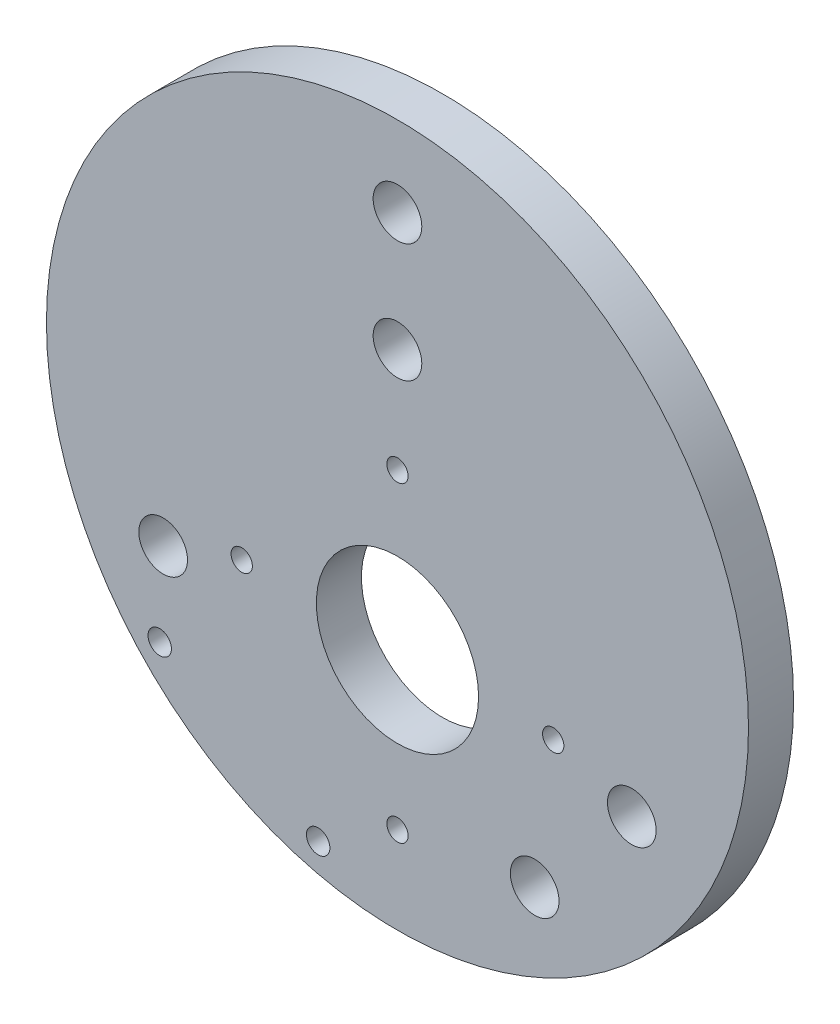
SolidWorks part; units mm, degrees
ref_plane "Front Plane" through (0, 0, 0) normal (0, 0, 1) x (1, 0, 0)
ref_plane "Top Plane" through (0, 0, 0) normal (0, 1, 0) x (1, 0, 0)
ref_plane "Right Plane" through (0, 0, 0) normal (1, 0, 0) x (0, 0, -1)
sketch "Sketch1" plane through (0, 0, 0) normal (0, 0, 1) x (1, 0, 0)
  circle A0 centre (0, 0) radius 49.4665
  dimension "D1" = 98.933
extrude "Boss-Extrude1" add sketch "Sketch1" along normal blind 6.35
sketch "Sketch2" plane through (0, 0, 6.35) normal (0, 0, 1) x (1, 0, 0)
  line L0 (0, -37.1877) -> (0, 6.7077) construction
  line L1 (-21.9477, -15.24) -> (0, 6.7077)
  line L2 (-21.9477, -15.24) -> (0, -37.1877)
  line L3 (0, -37.1877) -> (21.9477, -15.24)
  line L4 (0, 6.7077) -> (21.9477, -15.24)
  line L5 (0, -15.24) -> (12.0918, -15.24) construction
  point P4 (0, -15.24)
  dimension "D1" = 31.0388
  dimension "D2" = 31.0388
  dimension "D3" = 15.24
  dimension "D4" = 90
hole_wizard "M3 Screw Hole - Ø3.0mm Dowel Hole" positions "Sketch3" profile "Sketch4" hole size "Ø3.0" standard "ANSI Metric" end condition through all
sketch "Sketch3" plane through (0, 0, 6.35) normal (0, 0, 1) x (1, 0, 0)
  point P0 (0, 6.7077)
  point P3 (-21.9477, -15.24)
  point P6 (0, -37.1877)
  point P9 (21.9477, -15.24)
sketch "Sketch4" plane through (0, 6.7077, 6.35) normal (1, 0, 0) x (0, -1, 0)
  line L0 (0, 0) -> (0, 6.35)
  line L1 (0, 6.35) -> (1.5, 6.35)
  line L2 (1.5, 6.35) -> (1.5, 0)
  line L5 (1.5, 0) -> (0, 0)
  line L11 (0, -6.35) -> (0, 107.95) construction
  dimension "Thru Hole Dia." = 3
  dimension "Thru Hole Depth" = 6.35
sketch "Sketch5" plane through (0, 0, 6.35) normal (0, 0, 1) x (1, 0, 0)
  line L0 (0, -37.1877) -> (0, 6.7077) construction
  line L1 (-29.9941, -15.24) -> (0, 14.7541)
  line L2 (-29.9941, -15.24) -> (0, -45.2341)
  line L3 (0, -45.2341) -> (29.9941, -15.24)
  line L4 (0, 14.7541) -> (29.9941, -15.24)
  line L5 (-29.9941, -15.24) -> (29.9941, -15.24) construction
  line L6 (0, -45.2341) -> (0, 14.7541) construction
  line L7 (-19.3974, 4.1574) -> (0, -15.24) construction
  line L8 (0, -15.24) -> (19.3974, -15.24) construction
  line L9 (0, -15.24) -> (19.3974, -34.6374) construction
  line L10 (0, -15.24) -> (-3.0533, -18.2933) construction
  line L11 (-3.0533, -18.2933) -> (16.3441, -37.6906) construction
  line L12 (0, -15.24) -> (-19.3974, -34.6374) construction
  line L13 (0, -15.24) -> (-18.3197, 3.0797) construction
  line L14 (-18.3197, 3.0797) -> (0, 21.3994) construction
  circle A0 centre (0, 21.3994) radius 3.429
  circle A1 centre (16.3441, -37.6906) radius 3.429
  circle A2 centre (-19.3974, -34.6374) radius 3.429
  point P0 (0, -15.24)
  point P7 (0, -15.24)
  dimension "D3" = 27.432
  dimension "D5" = 27.432
  dimension "D9" = 6.858
  dimension "D1" = 42.418
  dimension "D2" = 4.318
  dimension "D4" = 42.418
  dimension "D6" = 27.432
  dimension "D7" = 135
  dimension "D8" = 25.908
sketch "Sketch6" plane through (0, 0, 6.35) normal (0, 0, 1) x (1, 0, 0)
  line L0 (0, 38.1282) -> (-33.02, -19.0641) construction
  line L1 (-33.02, -19.0641) -> (33.02, -19.0641) construction
  line L2 (33.02, -19.0641) -> (0, 38.1282) construction
  line L3 (-33.02, -19.0641) -> (0, 0) construction
  line L4 (0, 0) -> (33.02, -19.0641) construction
  line L5 (0, 0) -> (0, 38.1282) construction
  circle A0 centre (0, 38.1282) radius 3.429
  circle A1 centre (-33.02, -19.0641) radius 3.429
  circle A2 centre (33.02, -19.0641) radius 3.429
  dimension "D1" = 6.858
  dimension "D2" = 66.04
  dimension "D3" = 60
  dimension "D4" = 60
extrude "Cut-Extrude2" cut sketch "Sketch6" against normal through all
sketch "Sketch7" plane through (0, 0, 6.35) normal (0, 0, 1) x (1, 0, 0)
  line L0 (0, -37.1877) -> (0, 6.7077) construction
  circle A0 centre (0, -15.24) radius 11.43
  point P4 (0, -15.24)
  dimension "D1" = 22.86
extrude "Cut-Extrude3" cut sketch "Sketch7" against normal through all
sketch "Possible Plate Hole Reference" plane through (0, 0, 6.35) normal (0, 0, 1) x (1, 0, 0)
  line L0 (47.781, 12.8029) -> (-47.781, -12.8029) construction
  line L1 (0, 0) -> (49.4665, 0) construction
  circle A0 centre (0, 0) radius 49.4665 construction
  circle A1 centre (0, 0) radius 4.9466 construction
  circle A2 centre (0, 0) radius 49.4665 construction
  point P7 (0, 0)
  dimension "D2" = 9.8933
  dimension "D3" = 98.933
  dimension "D1" = 15
extrude "Cut-Extrude4" cut sketch "Sketch5" against normal through all contours A0 region at (0, 21.3994, 6.35)
sketch "Sketch11" plane through (0, 0, 6.35) normal (0, 0, 1) x (1, 0, 0)
  line L0 (0, 21.3994) -> (0, -59.7695) construction
  line L1 (0, 21.3994) -> (-33.5025, -31.0425) construction
  line L2 (-33.5025, -31.0425) -> (-11.176, -44.1861) construction
  line L3 (-11.176, -44.1861) -> (0, -44.1861) construction
  line L4 (0, 21.3994) -> (19.3378, -34.5341) construction
  line L5 (19.3378, -34.5341) -> (0, -34.5341) construction
  circle A0 centre (19.3378, -34.5341) radius 3.429
  circle A1 centre (-11.176, -44.1861) radius 1.651
  circle A2 centre (-33.5025, -31.0425) radius 1.651
  circle A3 centre (0, 21.3994) radius 3.429 construction
  dimension "D1" = 3.302
  dimension "D2" = 6.858
  dimension "D3" = 62.23
  dimension "D4" = 25.908
  dimension "D5" = 11.176
  dimension "D6" = 59.182
  dimension "D7" = 9.652
  dimension "D8" = 32.004
  dimension "D9" = 32.572
extrude "Cut-Extrude7" cut sketch "Sketch11" against normal through all
equation "\"D2@Possible Plate Hole Reference\" = 0.1 * \"D3@Possible Plate Hole Reference\""
